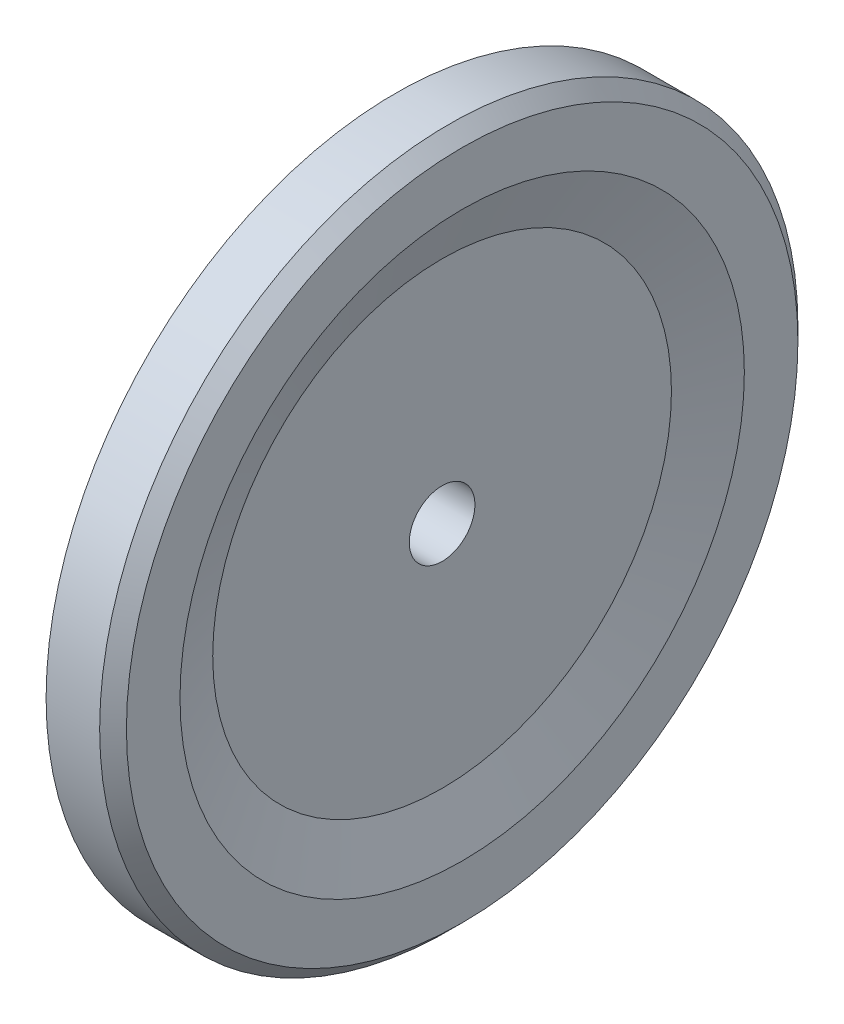
SolidWorks part; units mm, degrees
ref_plane "Front Plane" through (0, 0, 0) normal (0, 0, 1) x (1, 0, 0)
ref_plane "Top Plane" through (0, 0, 0) normal (0, 1, 0) x (1, 0, 0)
ref_plane "Right Plane" through (0, 0, 0) normal (1, 0, 0) x (0, 0, -1)
sketch "Sketch1" plane through (0, 0, 0) normal (0, 1, 0) x (1, 0, 0)
  line L1 (0, -28.6825) -> (0, 28.6825) construction
  line L2 (0, 4.9022) -> (0, 52.15)
  line L3 (0, 52.15) -> (10, 52.15)
  line L4 (10, 52.15) -> (10, 42.15)
  line L8 (7, 4.9022) -> (7, 34.26)
  line L9 (7, 34.26) -> (10, 42.15)
  line L10 (0, 4.9022) -> (7, 4.9022)
  dimension "D2" = 47.2478
  dimension "D3" = 10
  dimension "D4" = 10
  dimension "D6" = 29.3578
sketch "Sketch2" plane through (0, 0, 0) normal (0, 1, 0) x (1, 0, 0)
  line L0 (0, 0) -> (9.8109, 0)
  line L1 (-5.5, 0) -> (5.5, 0) construction
revolve "Revolve1" add sketch "Sketch1" angle 360 about L0
chamfer "Chamfer1" distance 2 angle 45 1 edges at (10, 0, 52.15)
